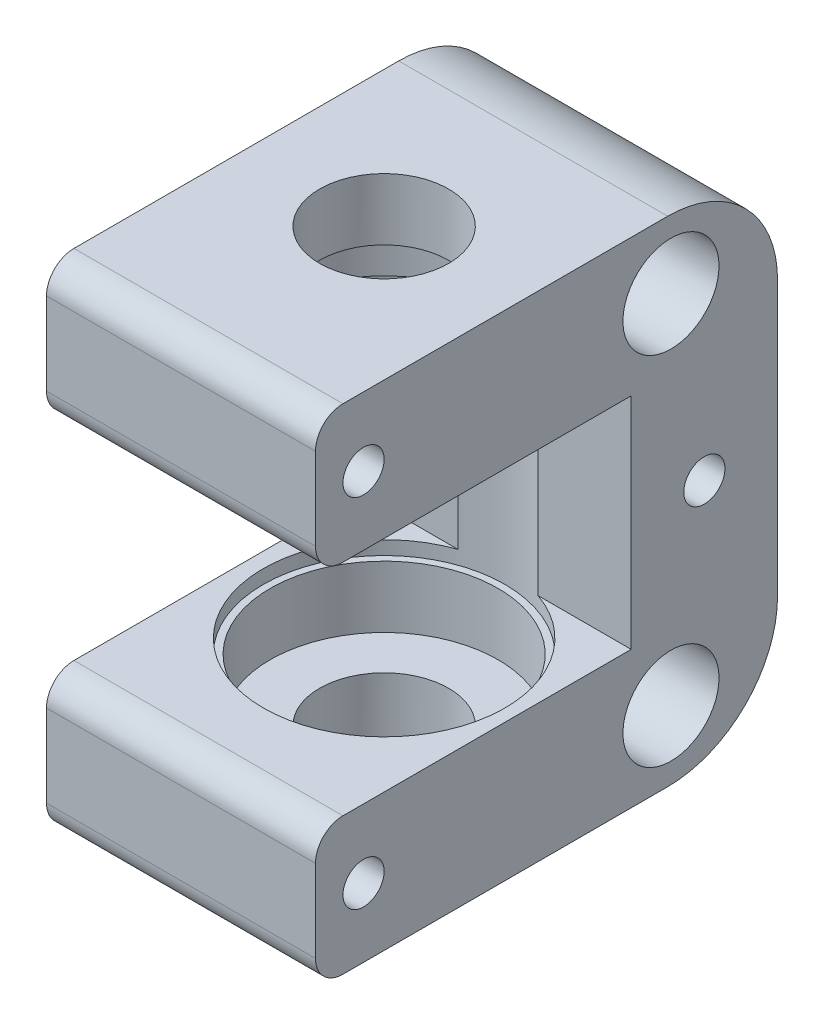
SolidWorks part; units mm, degrees
material "ABS"
ref_plane "Płaszczyzna przednia" through (0, 0, 0) normal (0, 0, 1) x (1, 0, 0)
ref_plane "Płaszczyzna górna" through (0, 0, 0) normal (0, 1, 0) x (1, 0, 0)
ref_plane "Płaszczyzna prawa" through (0, 0, 0) normal (1, 0, 0) x (0, 0, -1)
sketch "Szkic1" plane through (0, 0, 0) normal (0, 1, 0) x (1, 0, 0)
  line L0 (-27.62, 503.9124) -> (-27.62, -496.0876) construction
  line L1 (-12.98, 503.9124) -> (-12.98, -496.0876) construction
  line L2 (-20.3, 503.9124) -> (-20.3, -496.0876) construction
  line L3 (-44.2, 514.8847) -> (-44.2, 510.8628) construction
  line L4 (-44.7858, 509.4486) -> (-46.9, 507.3344) construction
  line L5 (-46.9, 507.3344) -> (-48.5, 507.3344) construction
  line L6 (-48.5, 507.3344) -> (-48.5, 509.7737) construction
  line L7 (-48.5, 509.7737) -> (-49.8, 509.7737) construction
  line L8 (-49.8, 509.7737) -> (-49.8, 509.4737) construction
  line L9 (-50, 509.2737) -> (-50.3, 509.2737) construction
  line L10 (-50.3, 509.2737) -> (-50.3, 504.3737) construction
  line L11 (-48.8, 502.8737) -> (-43.9, 502.8737) construction
  line L12 (-43.9, 502.8737) -> (-43.9, 503.1737) construction
  line L13 (-43.7, 503.3737) -> (-43.4, 503.3737) construction
  line L14 (-43.4, 503.3737) -> (-43.4, 504.6737) construction
  line L15 (-43.4, 504.6737) -> (-45.8393, 504.6737) construction
  line L16 (-45.8393, 504.6737) -> (-45.8393, 506.2737) construction
  line L17 (-45.8393, 506.2737) -> (-43.7251, 508.388) construction
  line L18 (-42.3109, 508.9737) -> (-38.2891, 508.9737) construction
  line L19 (-36.8749, 508.388) -> (-34.7606, 506.2737) construction
  line L20 (-34.7606, 506.2737) -> (-34.7606, 504.6737) construction
  line L21 (-34.7606, 504.6737) -> (-37.2, 504.6737) construction
  line L22 (-37.2, 504.6737) -> (-37.2, 503.3737) construction
  line L23 (-37.2, 503.3737) -> (-36.9, 503.3737) construction
  line L24 (-36.7, 503.1737) -> (-36.7, 502.8737) construction
  line L25 (-36.7, 502.8737) -> (-31.8, 502.8737) construction
  line L26 (-30.3, 504.3737) -> (-30.3, 509.2737) construction
  line L27 (-30.3, 509.2737) -> (-30.6, 509.2737) construction
  line L28 (-30.8, 509.4737) -> (-30.8, 509.7737) construction
  line L29 (-30.8, 509.7737) -> (-32.1, 509.7737) construction
  line L30 (-32.1, 509.7737) -> (-32.1, 507.3344) construction
  line L31 (-32.1, 507.3344) -> (-33.7, 507.3344) construction
  line L32 (-33.7, 507.3344) -> (-35.8142, 509.4486) construction
  line L33 (-36.4, 510.8628) -> (-36.4, 514.8847) construction
  line L34 (-35.8142, 516.2989) -> (-33.7, 518.4131) construction
  line L35 (-33.7, 518.4131) -> (-32.1, 518.4131) construction
  line L36 (-32.1, 518.4131) -> (-32.1, 515.9737) construction
  line L37 (-32.1, 515.9737) -> (-30.8, 515.9737) construction
  line L38 (-30.8, 515.9737) -> (-30.8, 516.2737) construction
  line L39 (-30.6, 516.4737) -> (-30.3, 516.4737) construction
  line L40 (-30.3, 516.4737) -> (-30.3, 521.3737) construction
  line L41 (-31.8, 522.8737) -> (-36.7, 522.8737) construction
  line L42 (-36.7, 522.8737) -> (-36.7, 522.5737) construction
  line L43 (-36.9, 522.3737) -> (-37.2, 522.3737) construction
  line L44 (-37.2, 522.3737) -> (-37.2, 521.0737) construction
  line L45 (-37.2, 521.0737) -> (-34.7606, 521.0737) construction
  line L46 (-34.7606, 521.0737) -> (-34.7606, 519.4737) construction
  line L47 (-34.7606, 519.4737) -> (-36.8749, 517.3595) construction
  line L48 (-38.2891, 516.7737) -> (-42.3109, 516.7737) construction
  line L49 (-43.7251, 517.3595) -> (-45.8393, 519.4737) construction
  line L50 (-45.8393, 519.4737) -> (-45.8393, 521.0737) construction
  line L51 (-45.8393, 521.0737) -> (-43.4, 521.0737) construction
  line L52 (-43.4, 521.0737) -> (-43.4, 522.3737) construction
  line L53 (-43.4, 522.3737) -> (-43.7, 522.3737) construction
  line L54 (-43.9, 522.5737) -> (-43.9, 522.8737) construction
  line L55 (-43.9, 522.8737) -> (-48.8, 522.8737) construction
  line L56 (-50.3, 521.3737) -> (-50.3, 516.4737) construction
  line L57 (-50.3, 516.4737) -> (-50, 516.4737) construction
  line L58 (-49.8, 516.2737) -> (-49.8, 515.9737) construction
  line L59 (-49.8, 515.9737) -> (-48.5, 515.9737) construction
  line L60 (-48.5, 515.9737) -> (-48.5, 518.4131) construction
  line L61 (-48.5, 518.4131) -> (-46.9, 518.4131) construction
  line L62 (-46.9, 518.4131) -> (-44.7858, 516.2989) construction
  line L63 (-30.3, 522.8737) -> (-30.3, 502.8737) construction
  line L64 (-30, 522.8737) -> (-30, 502.8737)
  line L65 (-20.3, 513.6124) -> (-25, 513.6124)
  line L66 (-25, 513.6124) -> (-25, 522.8737)
  line L67 (-30, 522.8737) -> (-25, 522.8737)
  line L68 (-20.3, 494.2124) -> (-30, 494.2124)
  line L69 (-30, 494.2124) -> (-30, 502.8737)
  line L70 (-20.3, 512.2124) -> (-30, 512.2124)
  line L71 (-30, 512.2124) -> (-30, 495.6124)
  line L72 (-30, 495.6124) -> (-20.3, 495.6124)
  circle A0 centre (-20.3, 503.9124) radius 7.2132 construction
  circle A1 centre (-20.3, 503.9124) radius 2.5 construction
  arc A2 (-44.7858, 509.4486) -> (-44.2, 510.8628) centre (-46.2, 510.8628) ccw construction
  arc A3 (-50, 509.2737) -> (-49.8, 509.4737) centre (-50, 509.4737) ccw construction
  arc A4 (-50.3, 504.3737) -> (-48.8, 502.8737) centre (-48.8, 504.3737) ccw construction
  arc A5 (-43.7, 503.3737) -> (-43.9, 503.1737) centre (-43.7, 503.1737) ccw construction
  arc A6 (-42.3109, 508.9737) -> (-43.7251, 508.388) centre (-42.3109, 506.9737) ccw construction
  arc A7 (-36.8749, 508.388) -> (-38.2891, 508.9737) centre (-38.2891, 506.9737) ccw construction
  arc A8 (-36.7, 503.1737) -> (-36.9, 503.3737) centre (-36.9, 503.1737) ccw construction
  arc A9 (-31.8, 502.8737) -> (-30.3, 504.3737) centre (-31.8, 504.3737) ccw construction
  arc A10 (-30.8, 509.4737) -> (-30.6, 509.2737) centre (-30.6, 509.4737) ccw construction
  arc A11 (-36.4, 510.8628) -> (-35.8142, 509.4486) centre (-34.4, 510.8628) ccw construction
  arc A12 (-35.8142, 516.2989) -> (-36.4, 514.8847) centre (-34.4, 514.8847) ccw construction
  arc A13 (-30.6, 516.4737) -> (-30.8, 516.2737) centre (-30.6, 516.2737) ccw construction
  arc A14 (-30.3, 521.3737) -> (-31.8, 522.8737) centre (-31.8, 521.3737) ccw construction
  arc A15 (-36.9, 522.3737) -> (-36.7, 522.5737) centre (-36.9, 522.5737) ccw construction
  arc A16 (-38.2891, 516.7737) -> (-36.8749, 517.3595) centre (-38.2891, 518.7737) ccw construction
  arc A17 (-43.7251, 517.3595) -> (-42.3109, 516.7737) centre (-42.3109, 518.7737) ccw construction
  arc A18 (-43.9, 522.5737) -> (-43.7, 522.3737) centre (-43.7, 522.5737) ccw construction
  arc A19 (-48.8, 522.8737) -> (-50.3, 521.3737) centre (-48.8, 521.3737) ccw construction
  arc A20 (-49.8, 516.2737) -> (-50, 516.4737) centre (-50, 516.2737) ccw construction
  arc A21 (-44.2, 514.8847) -> (-44.7858, 516.2989) centre (-46.2, 514.8847) ccw construction
  circle A22 centre (-20.3, 503.9124) radius 3
  circle A23 centre (-20.3, 503.9124) radius 8.3
  circle A24 centre (-20.3, 503.9124) radius 9.7
  arc A25 (-20.3, 512.2124) -> (-20.3, 495.6124) centre (-20.3, 503.9124) ccw
  dimension "D1" = 0.3
  dimension "D3" = 6
  dimension "D2" = 16.6
extrude "Dodanie-wyciągnięcie1" add sketch "Szkic1" along normal blind 60 contours A24 L65 L66 L67 L64 | A23 A22 | A24 A23 | A24 L64 L69 L68 | L70 A24 L72 A23 | A24 L70 L64 | A24 L72 L69 L68 region at (-27.3783, 0, -517.4017) region at (-28.682, 0, -510.2505) region at (-28.682, 0, -497.5743) region at (-28.5819, 0, -508.5822) region at (-22.8403, 0, -513.0213) region at (-26.7396, 0, -494.8388) region at (-14.597, 0, -509.6154)
extrude "Wytnij-wyciągnięcie1" cut sketch "Szkic1<4>" against normal blind 26 from offset 43 contours A23
sketch "Szkic1<4>" plane through (0, 0, 0) normal (0, 1, 0) x (1, 0, 0) same geometry as "Szkic1"
extrude "Wytnij-wyciągnięcie2" cut sketch "Szkic1<6>" against normal blind 16 from offset 38 contours L70 L71 L72 A25
sketch "Szkic1<6>" plane through (0, 0, 0) normal (0, 1, 0) x (1, 0, 0) same geometry as "Szkic1"
sketch "Szkic3" plane through (0, 60, 0) normal (0, 1, 0) x (1, 0, 0)
  line L0 (-25, 513.6124) -> (-25, 494.2124)
  line L1 (-20.3, 494.2124) -> (-30, 494.2124) construction
  line L2 (-20.3, 513.6124) -> (-25, 513.6124) construction
  line L3 (-20.3, 494.2124) -> (-25, 494.2124)
  line L4 (-20.3, 513.6124) -> (-25, 513.6124)
  arc A0 (-20.3, 494.2124) -> (-20.3, 513.6124) centre (-20.3, 503.9124) ccw construction
  arc A1 (-20.3, 494.2124) -> (-20.3, 513.6124) centre (-20.3, 503.9124) ccw
extrude "Wytnij-wyciągnięcie3" cut sketch "Szkic3" against normal blind 12
sketch "Szkic5" plane through (0, 0, 0) normal (0, -1, 0) x (1, 0, 0)
  line L3 (-25, -513.6124) -> (-20.3, -513.6124)
  line L4 (-25, -494.2124) -> (-25, -513.6124)
  line L5 (-20.3, -494.2124) -> (-25, -494.2124)
  line L6 (-25, -513.6124) -> (-20.3, -513.6124)
  line L7 (-25, -494.2124) -> (-25, -513.6124)
  line L8 (-20.3, -494.2124) -> (-25, -494.2124)
  arc A1 (-20.3, -513.6124) -> (-20.3, -494.2124) centre (-20.3, -503.9124) ccw
  arc A2 (-20.3, -513.6124) -> (-20.3, -494.2124) centre (-20.3, -503.9124) ccw
  dimension "D1" = 0
extrude "Wytnij-wyciągnięcie4" cut sketch "Szkic5" against normal blind 12
sketch "Szkic6" plane through (0, 48, 0) normal (0, 1, 0) x (1, 0, 0)
  line L3 (-20.3, 513.6124) -> (-25, 513.6124)
  line L4 (-25, 513.6124) -> (-25, 494.2124)
  line L5 (-25, 494.2124) -> (-20.3, 494.2124)
  line L6 (-20.3, 513.6124) -> (-25, 513.6124)
  line L7 (-25, 513.6124) -> (-25, 494.2124)
  line L8 (-25, 494.2124) -> (-20.3, 494.2124)
  arc A1 (-20.3, 494.2124) -> (-20.3, 513.6124) centre (-20.3, 503.9124) ccw
  arc A2 (-20.3, 494.2124) -> (-20.3, 513.6124) centre (-20.3, 503.9124) ccw
  dimension "D1" = 0
extrude "Wytnij-wyciągnięcie5" cut sketch "Szkic6" against normal blind 16 from offset 10 offset against normal yes
sketch "Szkic7" plane through (-25, 0, 0) normal (1, 0, 0) x (0, 0, -1)
  line L4 (495.6124, 38) -> (494.2124, 38)
  line L5 (494.2124, 38) -> (494.2124, 22)
  line L6 (494.2124, 22) -> (495.6124, 22)
  line L7 (495.6124, 22) -> (495.6124, 38)
  line L8 (495.6124, 38) -> (494.2124, 38)
  line L9 (494.2124, 38) -> (494.2124, 22)
  line L10 (494.2124, 22) -> (495.6124, 22)
  line L11 (495.6124, 22) -> (495.6124, 38)
  dimension "D1" = 0
extrude "Wytnij-wyciągnięcie6" cut sketch "Szkic7" against normal through all
sketch "Szkic8" plane through (-30, 0, 0) normal (-1, 0, 0) x (0, 0, 1)
  line L0 (-494.2124, 22) -> (-513.6124, 22) construction
  line L1 (-513.6124, 38) -> (-494.2124, 38) construction
  line L2 (-494.2124, 22) -> (-513.6124, 22) construction
  line L3 (-513.6124, 38) -> (-494.2124, 38) construction
  line L4 (-513.6124, 12) -> (-494.2124, 12) construction
  line L5 (-494.2124, 48) -> (-513.6124, 48) construction
  line L6 (-513.6124, 12) -> (-494.2124, 12) construction
  line L7 (-494.2124, 48) -> (-513.6124, 48) construction
  line L8 (-495.6124, 22) -> (-512.2124, 22) construction
  line L9 (-512.2124, 38) -> (-495.6124, 38) construction
  line L10 (-495.6124, 22) -> (-512.2124, 22)
  line L11 (-512.2124, 38) -> (-495.6124, 38)
  line L12 (-495.6124, 38) -> (-495.6124, 48) construction
  line L13 (-495.6124, 43) -> (-492.7124, 43) construction
  line L14 (-503.9124, 38) -> (-503.9124, 48) construction
  line L15 (-494.2124, 60) -> (-494.2124, 38) construction
  line L16 (-512.2124, 30) -> (-489.5852, 30) construction
  line L17 (-512.2124, 22) -> (-512.2124, 38) construction
  line L18 (-494.2124, 38) -> (-489.2124, 38)
  line L19 (-489.2124, 38) -> (-489.2124, 48)
  line L20 (-489.2124, 48) -> (-494.2124, 48)
  line L21 (-494.2124, 48) -> (-494.2124, 38)
  line L22 (-491.2124, 43) -> (-489.2124, 43) construction
  line L23 (-513.6124, 38) -> (-518.6124, 38)
  line L24 (-518.6124, 38) -> (-518.6124, 48)
  line L25 (-513.6124, 48) -> (-513.6124, 38)
  line L26 (-518.6124, 48) -> (-513.6124, 48)
  line L27 (-518.6124, 22) -> (-518.6124, 12)
  line L28 (-513.6124, 22) -> (-518.6124, 22)
  line L29 (-518.6124, 12) -> (-513.6124, 12)
  line L30 (-513.6124, 12) -> (-513.6124, 22)
  line L31 (-494.2124, 12) -> (-494.2124, 22)
  line L32 (-494.2124, 22) -> (-489.2124, 22)
  line L33 (-489.2124, 12) -> (-494.2124, 12)
  line L34 (-489.2124, 22) -> (-489.2124, 12)
  circle A0 centre (-492.7124, 43) radius 1.5
  circle A1 centre (-515.1124, 43) radius 1.5
  circle A2 centre (-515.1124, 17) radius 1.5
  circle A3 centre (-492.7124, 17) radius 1.5
  dimension "D1" = 3
  dimension "D2" = 2
extrude "Dodanie-wyciągnięcie2" add sketch "Szkic8" against normal blind 16 contours L20 L21 L18 L19 | L32 L34 L33 L31 | L26 L25 L23 L24 | L28 L27 L29 L30
sketch "Szkic9" plane through (0, 12, 0) normal (0, -1, 0) x (1, 0, 0)
  line L0 (-14, -513.6124) -> (-20.3, -513.6124) construction
  line L1 (-14, -494.2124) -> (-20.3, -494.2124) construction
  line L2 (-14, -513.6124) -> (-20.3, -513.6124)
  line L3 (-14, -494.2124) -> (-20.3, -494.2124)
  line L4 (-14, -494.2124) -> (-14, -496.5367)
  line L5 (-14, -511.288) -> (-14, -513.6124)
  arc A0 (-20.3, -513.6124) -> (-20.3, -494.2124) centre (-20.3, -503.9124) ccw construction
  arc A1 (-20.3, -513.6124) -> (-14, -511.288) centre (-20.3, -503.9124) ccw
  arc A2 (-14, -496.5367) -> (-20.3, -494.2124) centre (-20.3, -503.9124) ccw
extrude "Dodanie-wyciągnięcie3" add sketch "Szkic9" against normal up to surface (10 mm away) up to face at (-20.3, 22, -495.6124)
sketch "Szkic10" plane through (0, 38, 0) normal (0, -1, 0) x (1, 0, 0)
  line L0 (-14, -513.6124) -> (-20.3, -513.6124) construction
  line L1 (-14, -511.288) -> (-14, -513.6124) construction
  line L2 (-14, -494.2124) -> (-14, -496.5367) construction
  line L3 (-14, -494.2124) -> (-20.3, -494.2124) construction
  line L4 (-14, -513.6124) -> (-20.3, -513.6124)
  line L5 (-14, -511.288) -> (-14, -513.6124)
  line L6 (-14, -494.2124) -> (-14, -496.5367)
  line L7 (-14, -494.2124) -> (-20.3, -494.2124)
  arc A0 (-20.3, -513.6124) -> (-14, -511.288) centre (-20.3, -503.9124) ccw construction
  arc A1 (-14, -496.5367) -> (-20.3, -494.2124) centre (-20.3, -503.9124) ccw construction
  arc A2 (-20.3, -513.6124) -> (-14, -511.288) centre (-20.3, -503.9124) ccw
  arc A3 (-14, -496.5367) -> (-20.3, -494.2124) centre (-20.3, -503.9124) ccw
extrude "Dodanie-wyciągnięcie4" add sketch "Szkic10" against normal up to surface (10 mm away) up to face at (-20.3, 48, -500.9124)
sketch "Szkic11" plane through (-25, 0, 0) normal (1, 0, 0) x (0, 0, -1)
  line L0 (518.6124, 38) -> (512.2124, 38) construction
  line L1 (518.6124, 22) -> (512.2124, 22) construction
  line L2 (512.2124, 22) -> (512.2124, 38) construction
  line L3 (518.6124, 38) -> (512.2124, 38)
  line L4 (518.6124, 22) -> (512.2124, 22)
  line L5 (512.2124, 22) -> (512.2124, 38)
  line L6 (518.6124, 38) -> (518.6124, 22)
extrude "Dodanie-wyciągnięcie5" add sketch "Szkic11" along normal up to surface (11 mm away) up to face at (-14, 43, -514.9502)
sketch "Szkic12" plane through (0, 12, 0) normal (0, -1, 0) x (1, 0, 0)
  line L0 (-14, -518.6124) -> (-14, -511.288) construction
  line L1 (-14, -518.6124) -> (-14, -511.288)
  line L2 (-10.6, -503.9124) -> (-10.6, -518.6124)
  line L3 (-10.6, -518.6124) -> (-14, -518.6124)
  line L4 (-14, -489.2124) -> (-14, -496.5367) construction
  line L5 (-14, -489.2124) -> (-14, -496.5367)
  line L6 (-10.6, -503.9124) -> (-10.6, -489.2124)
  line L7 (-10.6, -489.2124) -> (-14, -489.2124)
  arc A0 (-14, -511.288) -> (-14, -496.5367) centre (-20.3, -503.9124) ccw construction
  arc A1 (-14, -511.288) -> (-10.6, -503.9124) centre (-20.3, -503.9124) ccw
  arc A2 (-10.6, -503.9124) -> (-14, -496.5367) centre (-20.3, -503.9124) ccw
  arc M1 (-14, -511.288) -> (-14, -496.5367) centre (-20.3, -503.9124) ccw
  line M2 (-14, -496.5367) -> (-14, -489.2124)
  line M8 (-14, -518.6124) -> (-14, -511.288)
extrude "Dodanie-wyciągnięcie6" add sketch "Szkic12" against normal up to surface (10 mm away) contours L6 L7 M2 M1 | L3 L2 M1 M8 region at (-12.1304, 12, -494.1542) region at (-12.1304, 12, -513.6705) up to face at (-19.15, 22, -502.3124)
sketch "Szkic13" plane through (0, 48, 0) normal (0, 1, 0) x (1, 0, 0)
  line L0 (-10.6, 489.2124) -> (-14, 489.2124) construction
  line L1 (-14, 489.2124) -> (-14, 496.5367) construction
  line L2 (-14, 518.6124) -> (-14, 511.288) construction
  line L3 (-10.6, 518.6124) -> (-14, 518.6124) construction
  line L4 (-10.6, 503.9124) -> (-10.6, 518.6124) construction
  line L5 (-10.6, 503.9124) -> (-10.6, 489.2124) construction
  line L6 (-10.6, 489.2124) -> (-14, 489.2124)
  line L7 (-14, 489.2124) -> (-14, 496.5367)
  line L8 (-14, 518.6124) -> (-14, 511.288)
  line L9 (-10.6, 518.6124) -> (-14, 518.6124)
  line L10 (-10.6, 503.9124) -> (-10.6, 518.6124)
  line L11 (-10.6, 503.9124) -> (-10.6, 489.2124)
  arc A0 (-14, 496.5367) -> (-10.6, 503.9124) centre (-20.3, 503.9124) ccw construction
  arc A1 (-10.6, 503.9124) -> (-14, 511.288) centre (-20.3, 503.9124) ccw construction
  arc A2 (-14, 496.5367) -> (-10.6, 503.9124) centre (-20.3, 503.9124) ccw
  arc A3 (-10.6, 503.9124) -> (-14, 511.288) centre (-20.3, 503.9124) ccw
  line M1 (-14, 489.2124) -> (-14, 496.5367)
  arc M2 (-14, 496.5367) -> (-14, 511.288) centre (-20.3, 503.9124) ccw
  line M3 (-14, 511.288) -> (-14, 518.6124)
extrude "Dodanie-wyciągnięcie7" add sketch "Szkic13" against normal blind 10 contours L10 L9 M2 M3 | L11 L6 M2 M1 region at (-12.1304, 48, -513.6705) region at (-12.1304, 48, -494.1542)
sketch "Szkic15" plane through (-14, 0, 0) normal (1, 0, 0) x (0, 0, -1)
  line L4 (518.6124, 38) -> (512.2124, 38)
  line L5 (518.6124, 38) -> (512.2124, 38)
  line L6 (512.2124, 38) -> (512.2124, 22)
  line L7 (512.2124, 38) -> (512.2124, 22)
  line L8 (518.6124, 22) -> (518.6124, 38)
  line L9 (518.6124, 22) -> (518.6124, 38)
  line L10 (512.2124, 22) -> (518.6124, 22)
  line L11 (512.2124, 22) -> (518.6124, 22)
  dimension "D1" = 0
extrude "Dodanie-wyciągnięcie8" add sketch "Szkic15" along normal up to surface (3.4 mm away) up to face at (-10.6, 43, -503.9124)
extrude "Wytnij-wyciągnięcie7" cut sketch "Szkic8<3>" against normal through all contours A0 | A1 | A3 | A2
sketch "Szkic8<3>" plane through (-30, 0, 0) normal (-1, 0, 0) x (0, 0, 1) same geometry as "Szkic8"
sketch "Szkic16" plane through (0, 48, 0) normal (0, 1, 0) x (1, 0, 0)
  circle A0 centre (-20.3, 503.9124) radius 4.7
extrude "Wytnij-wyciągnięcie8" cut sketch "Szkic16" against normal through all
sketch "Szkic17" plane through (0, 43, 0) normal (0, -1, 0) x (1, 0, 0)
  circle A1 centre (-20.3, -503.9124) radius 8.3
  circle A2 centre (-20.3, -503.9124) radius 8.3
  dimension "D1" = 0
extrude "Wytnij-wyciągnięcie9" cut sketch "Szkic17" against normal blind 0.5
sketch "Szkic18" plane through (0, 17, 0) normal (0, 1, 0) x (1, 0, 0)
  circle A1 centre (-20.3, 503.9124) radius 8.3
  circle A2 centre (-20.3, 503.9124) radius 8.3
  dimension "D1" = 0
extrude "Wytnij-wyciągnięcie10" cut sketch "Szkic18" against normal blind 0.5
sketch "Szkic19" plane through (-25, 0, 0) normal (1, 0, 0) x (0, 0, -1)
  line L0 (494.2124, 48) -> (522.8737, 48)
  line L1 (522.8737, 60) -> (522.8737, 0) construction
  line L2 (522.8737, 48) -> (522.8737, 60)
  line L3 (522.8737, 60) -> (494.2124, 60)
  line L4 (494.2124, 60) -> (494.2124, 48)
  line L5 (494.2124, 12) -> (522.8737, 12)
  line L6 (522.8737, 12) -> (522.8737, 0)
  line L7 (522.8737, 0) -> (494.2124, 0)
  line L8 (494.2124, 0) -> (494.2124, 12)
extrude "Wytnij-wyciągnięcie11" cut sketch "Szkic19" against normal through all
sketch "Szkic20" plane through (-25, 0, 0) normal (1, 0, 0) x (0, 0, -1)
  line L4 (518.6124, 48) -> (518.6124, 12)
  line L5 (518.6124, 12) -> (522.8737, 12)
  line L6 (522.8737, 12) -> (522.8737, 48)
  line L7 (522.8737, 48) -> (518.6124, 48)
  line L8 (518.6124, 48) -> (518.6124, 12)
  line L9 (518.6124, 12) -> (522.8737, 12)
  line L10 (522.8737, 12) -> (522.8737, 48)
  line L11 (522.8737, 48) -> (518.6124, 48)
  dimension "D1" = 0
extrude "Dodanie-wyciągnięcie9" add sketch "Szkic20" along normal up to surface (14.4 mm away) up to face at (-10.6, 17, -494.2124)
sketch "Szkic21" plane through (-10.6, 0, 0) normal (1, 0, 0) x (0, 0, -1)
  line L0 (512.2124, 30) -> (522.8737, 30) construction
  line L1 (512.2124, 38) -> (512.2124, 22) construction
  line L2 (522.8737, 12) -> (522.8737, 48) construction
  circle A5 centre (515.1124, 43) radius 1.8
  circle A6 centre (515.1124, 43) radius 1.8
  circle A7 centre (517.5431, 30) radius 1.5
  circle A8 centre (515.1124, 17) radius 1.8
  circle A9 centre (515.1124, 17) radius 1.8
  circle M4 centre (515.1124, 17) radius 1.5
  circle M14 centre (515.1124, 43) radius 1.5
  dimension "D1" = 0.3
  dimension "D2" = 0.3
extrude "Wytnij-wyciągnięcie12" cut sketch "Szkic21" against normal through all contours A6 M14 | A9 M4 region at (-10.6, 43, -513.3633) region at (-10.6, 17, -513.3633)
extrude "Wytnij-wyciągnięcie13" cut sketch "Szkic21<3>" against normal blind 16 contours A7
sketch "Szkic21<3>" plane through (-10.6, 0, 0) normal (1, 0, 0) x (0, 0, -1) same geometry as "Szkic21"
fillet "Zaokrąglenie1" radius 8 2 edges at (-20.3, 12, -522.8737) (-20.3, 48, -522.8737)
fillet "Zaokrąglenie2" radius 2 4 edges at (-20.3, 48, -489.2124) (-20.3, 12, -489.2124) (-20.3, 22, -489.2124) (-20.3, 38, -489.2124)
sketch "Szkic22" plane through (-10.6, 0, 0) normal (1, 0, 0) x (0, 0, -1)
  circle A0 centre (515.1124, 43) radius 3.5
  circle A1 centre (515.1124, 17) radius 3.5
extrude "Wytnij-wyciągnięcie14" cut sketch "Szkic22" against normal blind 5
sketch "Szkic23" plane through (0, 38, 0) normal (0, -1, 0) x (1, 0, 0)
  circle A2 centre (-20.3, -503.9124) radius 8.8
  circle A3 centre (-20.3, -503.9124) radius 8.8
  dimension "D1" = 0.5
extrude "Wytnij-wyciągnięcie15" cut sketch "Szkic23" against normal blind 1 and the other way blind 17
sketch "Szkic25" plane through (-30, 0, 0) normal (-1, 0, 0) x (0, 0, 1)
  line L8 (-489.2124, 40) -> (-489.2124, 46)
  line L9 (-491.2124, 48) -> (-514.8737, 48)
  line L10 (-522.8737, 40) -> (-522.8737, 20)
  line L11 (-514.8737, 12) -> (-491.2124, 12)
  line L12 (-489.2124, 14) -> (-489.2124, 20)
  line L13 (-491.2124, 22) -> (-512.2124, 22)
  line L14 (-512.2124, 22) -> (-512.2124, 38)
  line L15 (-512.2124, 38) -> (-491.2124, 38)
  line L16 (-489.2124, 40) -> (-489.2124, 46)
  line L17 (-491.2124, 48) -> (-514.8737, 48)
  line L18 (-522.8737, 40) -> (-522.8737, 20)
  line L19 (-514.8737, 12) -> (-491.2124, 12)
  line L20 (-489.2124, 14) -> (-489.2124, 20)
  line L21 (-491.2124, 22) -> (-512.2124, 22)
  line L22 (-512.2124, 22) -> (-512.2124, 38)
  line L23 (-512.2124, 38) -> (-491.2124, 38)
  arc A6 (-489.2124, 46) -> (-491.2124, 48) centre (-491.2124, 46) ccw
  arc A7 (-514.8737, 48) -> (-522.8737, 40) centre (-514.8737, 40) ccw
  arc A8 (-522.8737, 20) -> (-514.8737, 12) centre (-514.8737, 20) ccw
  arc A9 (-491.2124, 12) -> (-489.2124, 14) centre (-491.2124, 14) ccw
  arc A10 (-489.2124, 20) -> (-491.2124, 22) centre (-491.2124, 20) ccw
  arc A11 (-491.2124, 38) -> (-489.2124, 40) centre (-491.2124, 40) ccw
  arc A12 (-489.2124, 46) -> (-491.2124, 48) centre (-491.2124, 46) ccw
  arc A13 (-514.8737, 48) -> (-522.8737, 40) centre (-514.8737, 40) ccw
  arc A14 (-522.8737, 20) -> (-514.8737, 12) centre (-514.8737, 20) ccw
  arc A15 (-491.2124, 12) -> (-489.2124, 14) centre (-491.2124, 14) ccw
  arc A16 (-489.2124, 20) -> (-491.2124, 22) centre (-491.2124, 20) ccw
  arc A17 (-491.2124, 38) -> (-489.2124, 40) centre (-491.2124, 40) ccw
  dimension "D1" = 0
extrude "Dodanie-wyciągnięcie10" add sketch "Szkic25" along normal blind 0.2
sketch "Szkic24" plane through (-30.2, 0, 0) normal (-1, 0, 0) x (0, 0, 1)
  line L0 (-515.1124, 15.2) -> (-515.1124, 44.8) construction
  point P0 (-515.1124, 17)
  point P1 (-515.1124, 43)
